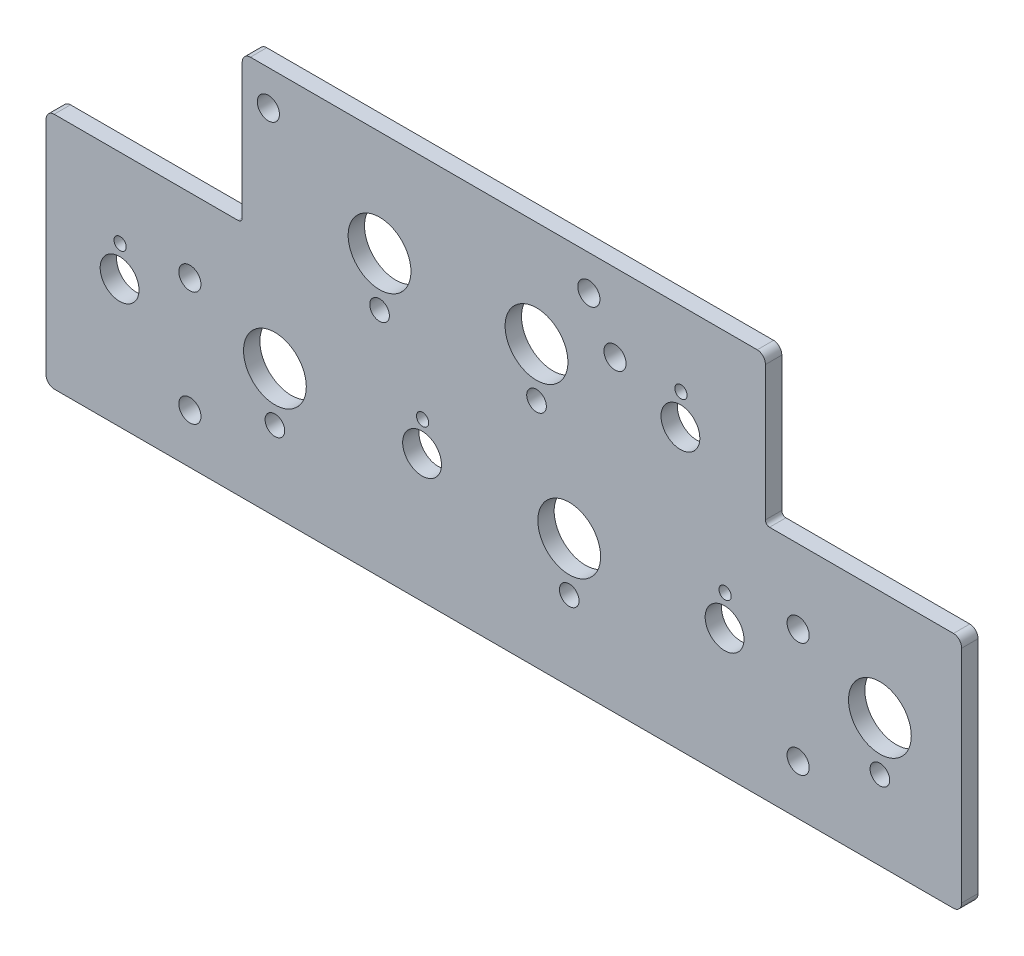
SolidWorks part; units mm, degrees
material "Acrylic (Medium-high impact)"
ref_plane "Front Plane" through (0, 0, 0) normal (0, 0, 1) x (1, 0, 0)
ref_plane "Top Plane" through (0, 0, 0) normal (0, 1, 0) x (1, 0, 0)
ref_plane "Right Plane" through (0, 0, 0) normal (1, 0, 0) x (0, 0, -1)
sketch "Sketch1" plane through (0, 0, 0) normal (0, 0, 1) x (1, 0, 0)
  line L8 (-51.5937, 5.4323) -> (-87.3125, 5.4323)
  line L9 (-88.9, 3.7429) -> (-88.9, -39.0998)
  line L10 (-87.3125, -40.7892) -> (87.3125, -40.7892)
  line L11 (88.9, -39.0998) -> (88.9, 3.7429)
  line L12 (87.3125, 5.4323) -> (51.5938, 5.4323)
  line L13 (50.8, 6.277) -> (50.8, 32.3948)
  line L14 (49.2125, 34.0842) -> (-49.2125, 34.0842)
  line L15 (-50.8, 32.3948) -> (-50.8, 6.277)
  line L16 (-51.5937, 5.4323) -> (-87.3125, 5.4323)
  line L17 (-88.9, 3.7429) -> (-88.9, -39.0998)
  line L18 (-87.3125, -40.7892) -> (87.3125, -40.7892)
  line L19 (88.9, -39.0998) -> (88.9, 3.7429)
  line L20 (87.3125, 5.4323) -> (51.5938, 5.4323)
  line L21 (50.8, 6.277) -> (50.8, 32.3948)
  line L22 (49.2125, 34.0842) -> (-49.2125, 34.0842)
  line L23 (-50.8, 32.3948) -> (-50.8, 6.277)
  ellipse E8 centre (87.3125, 3.7429) end of major axis (87.3125, 2.0535) minor radius 1.5875 (88.9, 3.7429) -> (87.3125, 5.4323) ccw
  ellipse E9 centre (87.3125, 3.7429) end of major axis (87.3125, 2.0535) minor radius 1.5875 (88.9, 3.7429) -> (87.3125, 5.4323) ccw
  ellipse E10 centre (49.2125, 32.3948) end of major axis (49.2125, 34.0842) minor radius 1.5875 (50.8, 32.3948) -> (49.2125, 34.0842) ccw
  ellipse E11 centre (49.2125, 32.3948) end of major axis (49.2125, 34.0842) minor radius 1.5875 (50.8, 32.3948) -> (49.2125, 34.0842) ccw
  ellipse E12 centre (51.5938, 6.277) end of major axis (51.5938, 5.4323) minor radius 0.7938 (50.8, 6.277) -> (51.5938, 5.4323) ccw
  ellipse E13 centre (51.5938, 6.277) end of major axis (51.5938, 5.4323) minor radius 0.7938 (50.8, 6.277) -> (51.5938, 5.4323) ccw
  ellipse E14 centre (-51.5937, 6.277) end of major axis (-51.5937, 5.4323) minor radius 0.7938 (-51.5937, 5.4323) -> (-50.8, 6.277) ccw
  ellipse E15 centre (-51.5937, 6.277) end of major axis (-51.5937, 5.4323) minor radius 0.7938 (-51.5937, 5.4323) -> (-50.8, 6.277) ccw
  ellipse E28 centre (-49.2125, 32.3948) end of major axis (-49.2125, 34.0842) minor radius 1.5875 (-49.2125, 34.0842) -> (-50.8, 32.3948) ccw
  ellipse E29 centre (-49.2125, 32.3948) end of major axis (-49.2125, 34.0842) minor radius 1.5875 (-49.2125, 34.0842) -> (-50.8, 32.3948) ccw
  ellipse E30 centre (-87.3125, 3.7429) end of major axis (-87.3125, 2.0535) minor radius 1.5875 (-87.3125, 5.4323) -> (-88.9, 3.7429) ccw
  ellipse E31 centre (-87.3125, 3.7429) end of major axis (-87.3125, 2.0535) minor radius 1.5875 (-87.3125, 5.4323) -> (-88.9, 3.7429) ccw
  ellipse E32 centre (-87.3125, -39.0998) end of major axis (-87.3125, -37.4104) minor radius 1.5875 (-88.9, -39.0998) -> (-87.3125, -40.7892) ccw
  ellipse E33 centre (-87.3125, -39.0998) end of major axis (-87.3125, -37.4104) minor radius 1.5875 (-88.9, -39.0998) -> (-87.3125, -40.7892) ccw
  ellipse E34 centre (87.3125, -39.0998) end of major axis (87.3125, -37.4104) minor radius 1.5875 (87.3125, -40.7892) -> (88.9, -39.0998) ccw
  ellipse E35 centre (87.3125, -39.0998) end of major axis (87.3125, -37.4104) minor radius 1.5875 (87.3125, -40.7892) -> (88.9, -39.0998) ccw
  dimension "D1" = 0
extrude "Boss-Extrude1" add sketch "Sketch1" along normal blind 3.175
sketch "Sketch2" plane through (0, 0, 3.175) normal (0, 0, 1) x (1, 0, 0)
  arc A4 (-72.0725, -25.0899) -> (-77.1525, -25.0899) centre (-74.6125, -15.9098) ccw construction
  arc A5 (-14.2875, -23.6221) -> (-17.4625, -23.6221) centre (-15.875, -15.9098) ccw construction
  arc A6 (45.4025, -25.0899) -> (40.3225, -25.0899) centre (42.8625, -15.9098) ccw construction
  arc A7 (35.8775, 5.9054) -> (32.7025, 5.9054) centre (34.29, 13.6177) ccw construction
  circle A8 centre (42.8625, -15.9098) radius 3.7703
  circle A9 centre (-15.875, -15.9098) radius 3.7703
  circle A10 centre (-74.6125, -15.9098) radius 3.7703
  circle A11 centre (34.29, 13.6177) radius 3.7703
  dimension "D1" = 7.5406
extrude "Cut-Extrude1" cut sketch "Sketch2" against normal through all
sketch "Sketch4" plane through (0, 0, 3.175) normal (0, 0, 1) x (1, 0, 0)
  circle A0 centre (73.025, -15.9098) radius 6.096
  circle A1 centre (12.7, -15.9098) radius 6.096
  circle A2 centre (-44.45, -15.9098) radius 6.096
  circle A3 centre (-24.13, 13.6177) radius 6.096
  circle A4 centre (6.35, 13.6177) radius 6.096
  circle A5 centre (73.025, -25.4348) radius 1.905
  circle A6 centre (12.7, -25.4348) radius 1.905
  circle A7 centre (-44.45, -25.4348) radius 1.905
  circle A8 centre (6.35, 4.0927) radius 1.905
  circle A9 centre (-24.13, 4.0927) radius 1.905
  dimension "D1" = 12.192
  dimension "D2" = 3.81
  dimension "D3" = 9.525
  dimension "D4" = 9.525
extrude "Cut-Extrude2" cut sketch "Sketch4" against normal through all
hole_wizard "#6 Clearance Hole1" positions "Sketch6" profile "Sketch5" hole size "#6" standard "ANSI Inch" end condition through all
sketch "Sketch6" plane through (0, 0, 3.175) normal (0, 0, 1) x (1, 0, 0)
  point P0 (-45.72, 27.2702)
  point P3 (16.51, 27.2702)
  point P6 (21.59, 19.0152)
  point P9 (57.15, -8.9248)
  point P12 (57.15, -31.1498)
  point P15 (-60.96, -31.1498)
  point P18 (-60.96, -8.9248)
sketch "Sketch5" plane through (-45.72, 27.2702, 3.175) normal (1, 0, 0) x (0, -1, 0)
  line L0 (0, 0) -> (0, 3.175)
  line L1 (0, 3.175) -> (2.1526, 3.175)
  line L2 (2.1526, 3.175) -> (2.1526, 0)
  line L5 (2.1526, 0) -> (0, 0)
  line L11 (0, -6.35) -> (0, 107.95) construction
  dimension "Thru Hole Dia." = 4.3053
  dimension "Thru Hole Depth" = 3.175
fillet "Fillet1" [suppressed] radius 1.5875
sketch "Sketch7" plane through (0, 0, 3.175) normal (0, 0, 1) x (1, 0, 0)
  circle A0 centre (42.967, -9.9107) radius 1.1906
  circle A1 centre (-15.774, -10.1107) radius 1.1906
  circle A2 centre (-74.508, -9.9107) radius 1.1906
  circle A3 centre (34.3945, 19.6168) radius 1.1906
  dimension "D1" = 2.3813
extrude "Cut-Extrude3" cut sketch "Sketch7" against normal through all
equation "\"D4@Sketch4\"=\"D3@Sketch4\""
